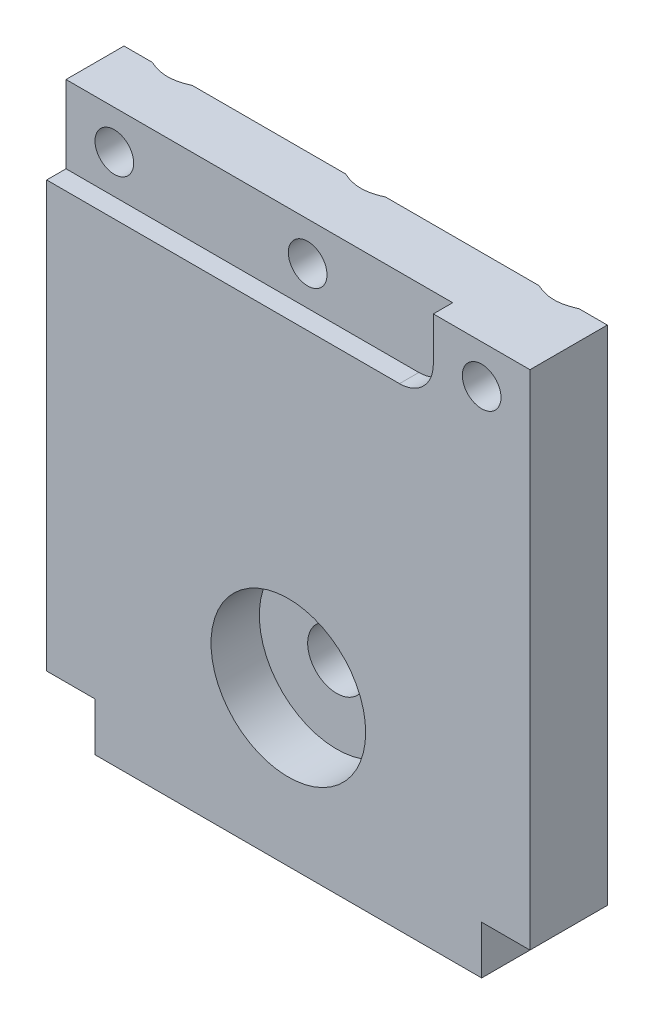
SolidWorks part; units mm, degrees
material "PVC rigide"
ref_plane "Plan de face" through (0, 0, 0) normal (0, 0, 1) x (1, 0, 0)
ref_plane "Plan de dessus" through (0, 0, 0) normal (0, 1, 0) x (1, 0, 0)
ref_plane "Plan de droite" through (0, 0, 0) normal (1, 0, 0) x (0, 0, -1)
sketch "Esquisse1" plane through (0, 0, 0) normal (0, 0, 1) x (1, 0, 0)
  line L0 (-25, -23.5) -> (-20, -23.5)
  line L1 (-25, 28.5) -> (25, 28.5)
  line L2 (-25, 28.5) -> (-25, -23.5)
  line L3 (-20, -28.5) -> (20, -28.5)
  line L4 (25, 28.5) -> (25, -23.5)
  line L5 (-20, -23.5) -> (-20, -28.5)
  line L6 (25, -23.5) -> (20, -23.5)
  line L7 (20, -23.5) -> (20, -28.5)
  line L8 (25, -28.5) -> (25, -23.5) construction
  line L9 (25, -28.5) -> (20, -28.5) construction
  line L10 (-25, -23.5) -> (-25, -28.5) construction
  line L11 (-25, -28.5) -> (-20, -28.5) construction
  line L12 (25, 28.5) -> (-25, -28.5) construction
  line L13 (-25, 28.5) -> (25, -28.5) construction
  point P9 (0, 0)
  dimension "D4" = 5
  dimension "D1" = 50
  dimension "D2" = 57
  dimension "D3" = 5
extrude "Boss.-Extru.1" add sketch "Esquisse1" along normal blind 8
sketch "Esquisse2" plane through (0, -28.5, 0) normal (0, -1, 0) x (1, 0, 0)
  line L0 (-25, 4) -> (25, 4) construction
  line L1 (-25, 8) -> (-25, 0) construction
  line L2 (25, 8) -> (25, 0) construction
  circle A0 centre (-15, 4) radius 2
  circle A1 centre (15, 4) radius 2
  dimension "D1" = 4
  dimension "D2" = 10
  dimension "D3" = 10
extrude "Enlèv. mat.-Extru.1" cut sketch "Esquisse2" against normal blind 10
sketch "Esquisse3" plane through (0, 0, 8) normal (0, 0, 1) x (1, 0, 0)
  line L0 (-25.973, 24.5) -> (39.229, 24.5) construction
  line L1 (25, 28.5) -> (-25, 28.5) construction
  line L2 (-25, 28.5) -> (-25, -23.5) construction
  line L3 (25, -23.5) -> (25, 28.5) construction
  circle A0 centre (-20, 24.5) radius 2
  circle A1 centre (20, 24.5) radius 2
  circle A2 centre (0, 24.5) radius 2
  point P14 (0, 24.5)
  dimension "D2" = 4
  dimension "D1" = 4
  dimension "D3" = 5
  dimension "D4" = 5
extrude "Enlèv. mat.-Extru.2" cut sketch "Esquisse3" against normal through all
chamfer "Chanfrein1" distance 2.5 angle 45 3 edges at (22, 24.5, 0) (-18, 24.5, 0) (2, 24.5, 0)
sketch "Esquisse4" plane through (0, 0, 8) normal (0, 0, 1) x (1, 0, 0)
  line L0 (-32.372, -12.5) -> (112.9613, -12.5) construction
  line L1 (0, -17.2825) -> (0, 28.5) construction
  line L3 (-20, -28.5) -> (20, -28.5) construction
  line L4 (25, 28.5) -> (-25, 28.5) construction
  circle A0 centre (0, -12.5) radius 8
  point P17 (0, -12.5)
  dimension "D1" = 16
  dimension "D2" = 16
extrude "Enlèv. mat.-Extru.3" cut sketch "Esquisse4" against normal blind 5
sketch "Esquisse5" plane through (0, 0, 3) normal (0, 0, 1) x (1, 0, 0)
  circle A0 centre (0, -12.5) radius 3
  circle A1 centre (0, -12.5) radius 8 construction
  dimension "D1" = 6
extrude "Enlèv. mat.-Extru.4" cut sketch "Esquisse5" against normal through all
sketch "Esquisse6" plane through (0, 0, 8) normal (0, 0, 1) x (1, 0, 0)
  line L1 (-25, 28.5) -> (15, 28.5)
  line L2 (-25, 28.5) -> (-25, 20.5)
  line L3 (-25, 20.5) -> (15, 20.5)
  line L5 (15, 20.5) -> (15, 28.5)
  circle A0 centre (-20, 24.5) radius 2 construction
  dimension "D1" = 4
extrude "Enlèv. mat.-Extru.5" cut sketch "Esquisse6" against normal blind 2
fillet "Congé1" radius 3.5 1 edges at (15, 20.5, 7)
